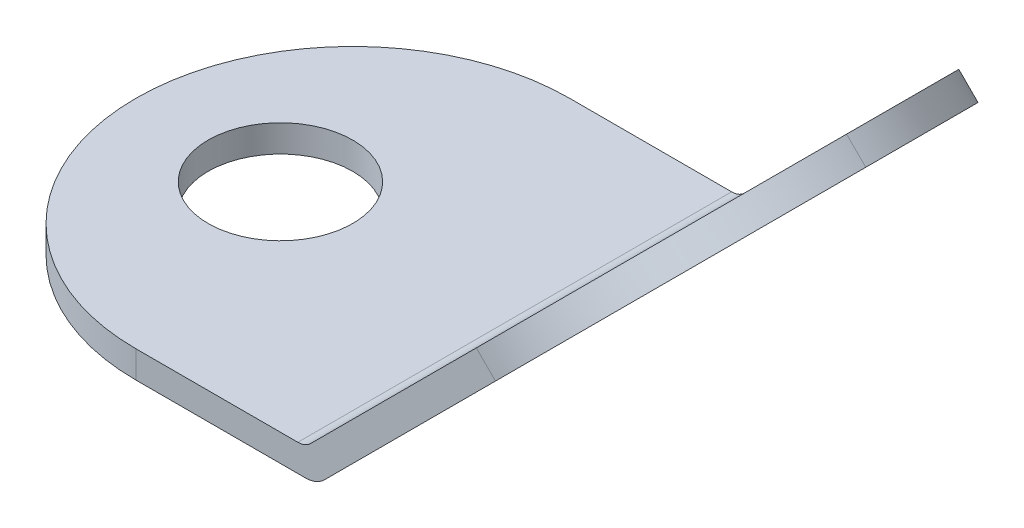
SolidWorks part; units mm, degrees
ref_plane "Piano frontale" through (0, 0, 0) normal (0, 0, 1) x (1, 0, 0)
ref_plane "Piano superiore" through (0, 0, 0) normal (0, 1, 0) x (1, 0, 0)
ref_plane "Piano destro" through (0, 0, 0) normal (1, 0, 0) x (0, 0, -1)
sketch "Schizzo1" plane through (0, 0, 0) normal (0, 0, 1) x (1, 0, 0)
  line L0 (9.1924, 9.1924) -> (0, 0)
  line L1 (0, 0) -> (-11, 0)
  dimension "D1" = 13
  dimension "D2" = 11
  dimension "D3" = 135
extrude "Estrusione-Sottile1" add sketch "Schizzo1" along normal mid plane 12 thin contours L0 L1 thin type one direction wall 0.75
fillet "Raccordo3" radius 6 4 edges at (-11, 0.375, 6) (-11, 0.375, -6) (8.9272, 9.4576, -6) (8.9272, 9.4576, 6)
sketch "Schizzo4" plane through (0, 0.75, 0) normal (0, 1, 0) x (1, 0, 0)
  circle A2 centre (-7, 0) radius 2
  point P0 (-5.8105, -0.1666)
  dimension "D1" = 4
  dimension "D2" = 4
extrude "Taglio-Estrusione1" cut sketch "Schizzo4" against normal up to surface (0.75 mm away) up to face at (-4.6971, 0, 0)
sketch "Schizzo5" plane through (-0.5303, 0.5303, 0) normal (-0.7071, 0.7071, 0) x (0, 0, 1)
  line L0 (0, 9) -> (0, 3.5) construction
  line L1 (2, 9) -> (2, 3.5)
  line L2 (-2, 9) -> (-2, 3.5)
  arc A0 (2, 9) -> (-2, 9) centre (0, 9) ccw
  arc A1 (-2, 3.5) -> (2, 3.5) centre (0, 3.5) ccw
  point P3 (0, 6.25)
  point P9 (0, 11)
  point P10 (0, 4.3327)
  point P11 (0, 1.5)
  dimension "D1" = 2
  dimension "D2" = 2
  dimension "D3" = 1.5
extrude "Taglio-Estrusione2" cut sketch "Schizzo5" against normal up to surface (0.75 mm away) up to face at (4.1698, 4.1698, 0)
fillet "Raccordo1" radius 0.75 1 edges at (0, 0, 0)
fillet "Raccordo2" radius 0.5 1 edges at (-0.3107, 0.75, 0)
